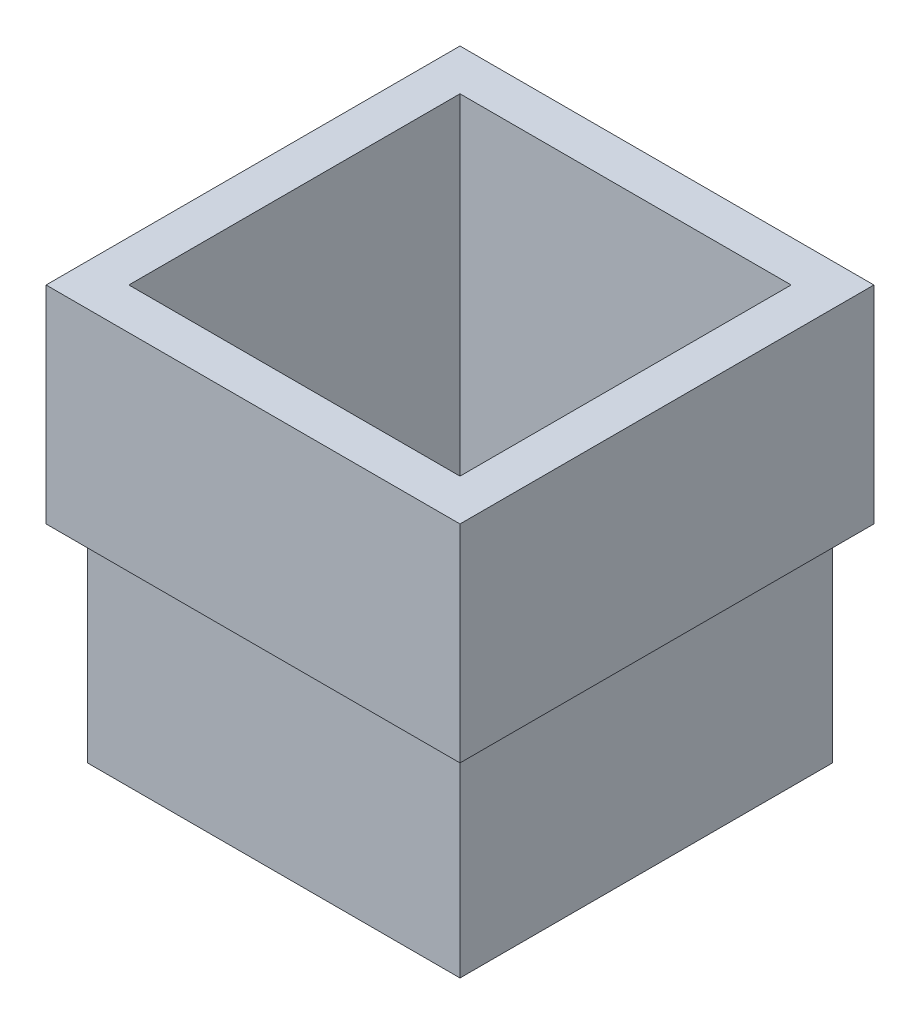
SolidWorks part; units mm, degrees
material "Delrin 2700 NC010, Low Viscosity Acetal Copolymer (SS)"
ref_plane "Front" through (0, 0, 0) normal (0, 0, 1) x (1, 0, 0)
ref_plane "Top" through (0, 0, 0) normal (0, 1, 0) x (1, 0, 0)
ref_plane "Right" through (0, 0, 0) normal (1, 0, 0) x (0, 0, -1)
sketch "Sketch1" plane through (0, 0, 0) normal (0, 1, 0) x (1, 0, 0)
  line L0 (22.5, -22.5) -> (22.5, 22.5)
  line L1 (-25, -25) -> (25, -25)
  line L2 (-25, -25) -> (-25, 25)
  line L3 (-25, 25) -> (25, 25)
  line L4 (25, -25) -> (25, 25)
  line L5 (-25, -25) -> (25, 25) construction
  line L6 (-25, 25) -> (25, -25) construction
  line L7 (-20, -20) -> (20, -20)
  line L8 (-20, -20) -> (-20, 20)
  line L9 (-20, 20) -> (20, 20)
  line L10 (20, -20) -> (20, 20)
  line L11 (-20, -20) -> (20, 20) construction
  line L12 (-20, 20) -> (20, -20) construction
  line L13 (-22.5, 22.5) -> (22.5, 22.5)
  line L14 (-22.5, -22.5) -> (-22.5, 22.5)
  line L15 (-22.5, -22.5) -> (22.5, -22.5)
  point P0 (0, 0)
  point P6 (0, 0)
  dimension "D1" = 50
  dimension "D2" = 5
  dimension "D3" = 2.5
extrude "Boss-Extrude1" add sketch "Sketch1" along normal blind 25 contours L14 L15 L0 L13 L10 L7 L8 L9 | L1 L4 L3 L2 L15 L14 L13 L0 region at (0, 0, 21.8636) region at (-24.2929, 0, 0)
extrude "Boss-Extrude2" add sketch "Sketch1<3>" against normal blind 25 contours L14 L15 L0 L13 L10 L7 L8 L9 region at (0, 0, 21.8636)
sketch "Sketch1<3>" plane through (0, 0, 0) normal (0, 1, 0) x (1, 0, 0) same geometry as "Sketch1"
